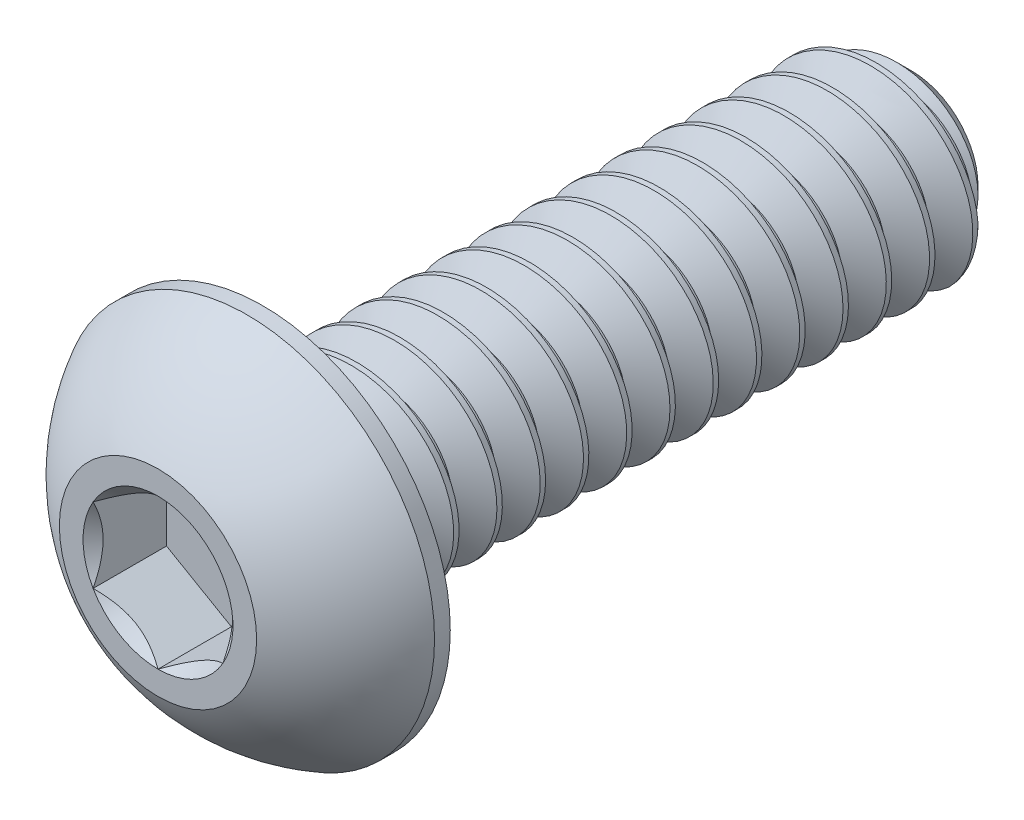
SolidWorks part; units mm, degrees
ref_plane "Front" through (0, 0, 0) normal (0, 0, 1) x (1, 0, 0)
ref_plane "Top" through (0, 0, 0) normal (0, 1, 0) x (1, 0, 0)
ref_plane "Right" through (0, 0, 0) normal (1, 0, 0) x (0, 0, -1)
sketch "Sketch1" plane through (0, 0, 0) normal (1, 0, 0) x (0, 0, -1)
  line L2 (2.5654, 2.413) -> (18.4404, 2.413)
  line L3 (18.4404, 2.413) -> (18.4404, 0)
  line L4 (18.4404, 0) -> (2.5654, 0)
  line L6 (2.1806, 4.5847) -> (2.5654, 4.5847) construction
  line L7 (18.4404, 2.413) -> (18.4404, -2.413) construction
  line L8 (0, 0) -> (2.5654, 0) construction
  line L9 (2.5654, 4.5847) -> (2.5654, -4.5847) construction
  line L11 (2.5654, 2.413) -> (2.5654, 0)
  line L13 (0, 1.5875) -> (0, -1.5875) construction
  line L14 (0, 1.5875) -> (0, 2.413) construction
  arc A3 (0, 2.413) -> (2.1806, 4.5847) centre (4.5749, 0) cw construction
  dimension "D1" = 0.3848
revolve "Revolve1" add sketch "Sketch1" angle 360 mid plane about L4
sketch "Sketch3" plane through (0, 0, -18.4404) normal (0, 0, -1) x (-1, 0, 0)
  circle A0 centre (0, 0) radius 2.413
curve "Helix/Spiral1" pitch 1.0583 height 16.9333 turns 16
sketch "Sketch2" plane through (0, 0, 0) normal (1, 0, 0) x (0, 0, -1)
  line L0 (18.4404, 2.413) -> (19.3664, 2.413)
  line L1 (19.3664, 2.413) -> (18.9696, 1.7256)
  line L2 (18.9696, 1.7256) -> (18.8373, 1.7256)
  line L3 (18.8373, 1.7256) -> (18.4404, 2.413)
  line L4 (18.6388, 2.0693) -> (19.168, 2.0693) construction
  dimension "D1" = 60
  dimension "D2" = 0.1323
  dimension "D3" = 0.5292
chamfer "Chamfer1" distance 0.7937 angle 45 1 edges at (0, 2.413, -18.4404)
sweep "Cut-Sweep1" cut profiles "Sketch2" path "Helix/Spiral1" align with end faces yes
sketch "Sketch7" plane through (0, 0, 0) normal (1, 0, 0) x (0, 0, -1)
  line L6 (2.1806, 4.5847) -> (2.5654, 4.5847) construction
  line L8 (0, 0) -> (2.5654, 0) construction
  line L11 (2.5654, 4.5847) -> (2.5654, -4.5847) construction
  line L12 (2.1806, 4.5847) -> (2.5654, 4.5847)
  line L13 (0, 0) -> (2.5654, 0)
  line L14 (0, 1.5875) -> (0, -1.5875) construction
  line L15 (2.5654, 4.5847) -> (2.5654, 0)
  line L16 (0, 2.413) -> (0, 0)
  arc A2 (2.1806, 4.5847) -> (0, 2.413) centre (4.5749, 0) ccw construction
  arc A3 (2.1806, 4.5847) -> (0, 2.413) centre (4.5749, 0) ccw
revolve "Revolve2" add sketch "Sketch7" angle 360 mid plane about L13
sketch "Sketch5" plane through (0, 0, 0) normal (0, 0, 1) x (1, 0, 0)
  line L1 (1.5875, -0.9165) -> (1.5875, 0.9165)
  line L2 (1.5875, 0.9165) -> (0, 1.8331)
  line L3 (0, 1.8331) -> (-1.5875, 0.9165)
  line L4 (-1.5875, 0.9165) -> (-1.5875, -0.9165)
  line L5 (-1.5875, -0.9165) -> (0, -1.8331)
  line L6 (0, -1.8331) -> (1.5875, -0.9165)
  circle A0 centre (0, 0) radius 1.5875 construction
extrude "Cut-Extrude2" cut sketch "Sketch5" against normal blind 1.7958
sketch "Sketch6" plane through (0, 0, 0) normal (0, 0, 1) x (1, 0, 0)
  circle A0 centre (0, 0) radius 1.8331
extrude "Cut-Extrude3" cut sketch "Sketch6" against normal blind 1.7958 draft 45
sketch "Sketch9" [suppressed] plane through (0, 0, -2.2098) normal (0, 0, 1) x (1, 0, 0)
  circle A2 centre (0, 0) radius 2.0828
extrude "Boss-Extrude2" [suppressed] add sketch "Sketch9" against normal offset from surface (3.175 mm away) 22.225
sketch "Sketch10" plane through (0, 0, 0) normal (1, 0, 0) x (0, 0, -1)
  line L0 (18.4404, 2.413) -> (18.4404, -2.413) construction
  point P0 (16.8529, -2.413)
  dimension "D1" = 1.5875
equation "\"D3@Helix/Spiral1\" = \"Lg@Sketch1\" + \"D4@Helix/Spiral1\""
equation "\"D2@Sketch2\" = \"D4@Helix/Spiral1\" * .125"
equation "\"D3@Sketch2\" = \"D4@Helix/Spiral1\" * .5"
equation "\"D1@Chamfer1\" = \"D4@Helix/Spiral1\" * .75"
equation "\"D1@Cut-Extrude2\" = \"Head Ht@Sketch1\" * .7"
equation "\"D1@Sketch1\" = \"Head Ht@Sketch1\" * .15"
equation "\"D1@Sketch10\" = \"D4@Helix/Spiral1\" * 1.5"
equation "\"D1@Cut-Extrude3\" = \"D1@Cut-Extrude2\""
